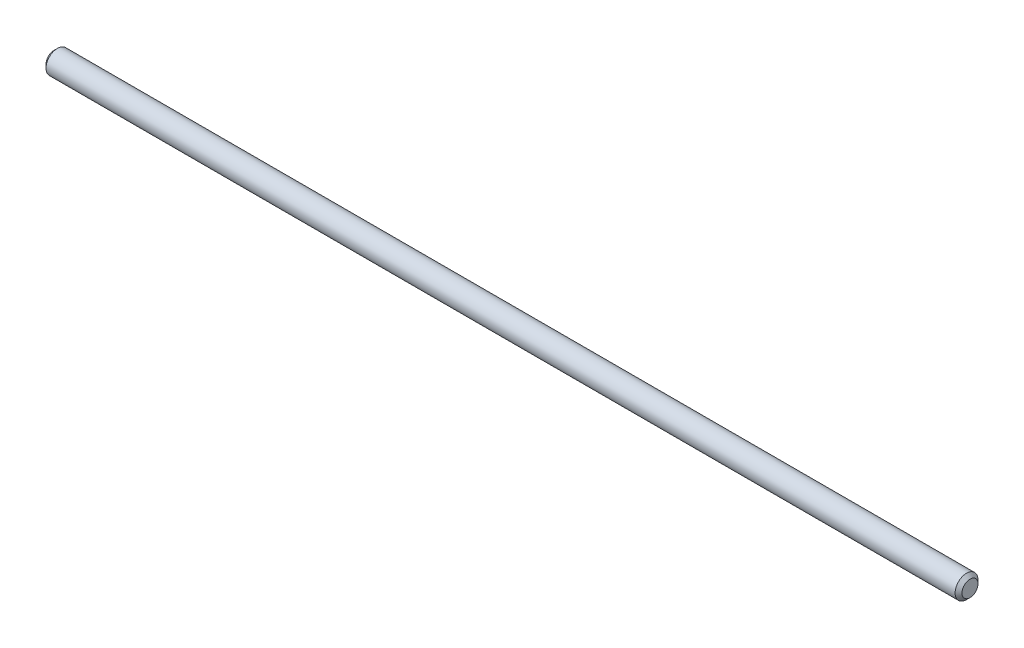
SolidWorks part; units mm, degrees
ref_plane "Front Plane" through (0, 0, 0) normal (0, 0, 1) x (1, 0, 0)
ref_plane "Top Plane" through (0, 0, 0) normal (0, 1, 0) x (1, 0, 0)
ref_plane "Right Plane" through (0, 0, 0) normal (1, 0, 0) x (0, 0, -1)
sketch "Sketch1" plane through (0, 0, 0) normal (0, 0, 1) x (1, 0, 0)
  line L0 (-127, 0) -> (127, 0) construction
  line L1 (127, 3.175) -> (127, -3.175) construction
  line L2 (-127, 3.175) -> (-127, -3.175) construction
  line L3 (-128.1906, 3.3125) -> (-126.9206, 3.3125) construction
  line L4 (-126.9206, 3.3125) -> (-127.5556, 2.2126) construction
  line L5 (-127.5556, 2.2126) -> (-128.1906, 3.3125) construction
  line L6 (-127.5556, 3.3125) -> (-127.5556, 3.175) construction
  line L7 (-127.635, 2.3501) -> (-127.4763, 2.3501) construction
  line L8 (-127.5556, 2.3501) -> (-127.5556, 2.2126) construction
  line L9 (-128.1509, 3.2437) -> (-126.9603, 3.2437) construction
  line L10 (-128.1113, 3.175) -> (-127, 3.175) construction
  line L11 (-121.285, 3.175) -> (121.285, 3.175) construction
  line L12 (0, 0) -> (0, 3.175) construction
  line L13 (-121.285, 3.175) -> (-121.285, -3.175) construction
  line L15 (121.285, 3.175) -> (121.285, -3.175) construction
  point P6 (-122.555, -3.175)
  point P8 (-107.95, 0)
  point P17 (-127.5556, 3.2437)
  dimension "Thread Diameter" = 6.35
  dimension "Length" = 254
  dimension "Segment" = 19.05
  dimension "Pitch" = 1.27
  dimension "D3" = 0.1588
  dimension "D1" = 4.445
  dimension "D2" = 5.715
sketch "Sketch2" plane through (0, 0, 0) normal (1, 0, 0) x (0, 0, -1)
  circle A0 centre (0, 0) radius 3.175
extrude "Boss-Extrude1" add sketch "Sketch2" against normal up to vertex (127 mm away) and the other way up to vertex (127 mm away) up to point (-127, 0, 0) other way up to point (127, 0, 0)
sketch "Sketch3" plane through (-127, 0, 0) normal (1, 0, 0) x (0, 0, -1)
  circle A1 centre (0, 0) radius 3.175
  circle A2 centre (0, 0) radius 3.175
  dimension "D1" = 0
chamfer "Chamfer1" distance 0.9525 angle 45 2 edges at (-127, 0, -3.175) (127, 0, -3.175)
curve "Helix/Spiral1" [suppressed] pitch 1.27 height 19.05 turns 15 parameters "Pitch"=1.27
sketch "Sketch4" plane through (0, 0, 0) normal (0, 0, 1) x (1, 0, 0)
  line L0 (-128.1509, 3.2437) -> (-126.9603, 3.2437)
  line L1 (-126.9603, 3.2437) -> (-127.4763, 2.3501)
  line L2 (-127.4763, 2.3501) -> (-127.635, 2.3501)
  line L3 (-127.635, 2.3501) -> (-128.1509, 3.2437)
sweep "Cut-Sweep3" [suppressed] cut profiles "Sketch4" path "Helix/Spiral1"
pattern_linear "LPattern1" [suppressed] of bodies 102
equation "\"D3@Helix/Spiral1\"=\"Segment@Sketch1\""
equation "\"D1@Chamfer1\"=\"Pitch@Sketch1\"*.75"
equation "\"D3@Sketch1\"=\"Pitch@Sketch1\"/8"
equation "\"Segment@Sketch1\"=\"Pitch@Sketch1\" * 15"
equation "\"Pitch@Helix/Spiral1\"=\"Pitch@Sketch1\""
equation "\"D3@LPattern1\"=\"Segment@Sketch1\"-\"Pitch@Sketch1\""
equation "\"Segments@LPattern1\" = \"Length@Sketch1\"/\"Segment@Sketch1\"+1"
equation "\"D1@Sketch1\"=\"Pitch@Sketch1\"*3.5"
equation "\"D2@Sketch1\"=\"Thread Diameter@Sketch1\"*.9"
